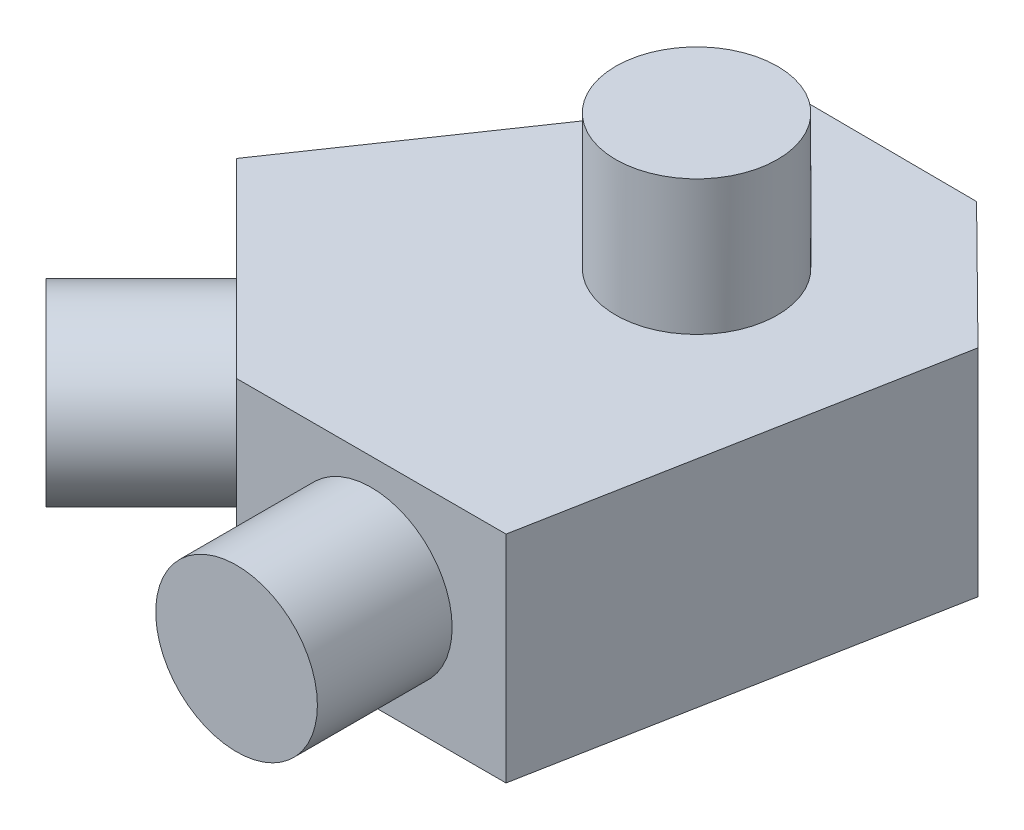
SolidWorks part; units mm, degrees
ref_plane "Front Plane" through (0, 0, 0) normal (0, 0, 1) x (1, 0, 0)
ref_plane "Top Plane" through (0, 0, 0) normal (0, 1, 0) x (1, 0, 0)
ref_plane "Right Plane" through (0, 0, 0) normal (1, 0, 0) x (0, 0, -1)
sketch "Sketch1" plane through (0, 0, 0) normal (0, 1, 0) x (1, 0, 0)
  line L0 (-8.9803, 8.9803) -> (0, 0)
  line L1 (0, 0) -> (12.7, 0)
  line L2 (-8.9803, 8.9803) -> (1.7691, 24.7077)
  line L3 (1.7691, 24.7077) -> (10.2143, 24.6596)
  line L4 (10.2143, 24.6596) -> (16.2201, 18.722)
  line L5 (16.2201, 18.722) -> (12.7, 0)
  line L6 (0, 0) -> (15.9814, 38.5826) construction
  dimension "D1" = 135
  dimension "D2" = 12.7
  dimension "D3" = 12.7
  dimension "D4" = 67.5
  dimension "D5" = 8.4454
  dimension "D6" = 8.4454
  dimension "D7" = 19.05
  dimension "D8" = 19.05
extrude "Boss-Extrude1" add sketch "Sketch1" along normal blind 10.16
sketch "Sketch2" plane through (0, 0, 0) normal (0, 0, 1) x (1, 0, 0)
  line L0 (0, 5.08) -> (15.0157, 5.08) construction
  line L1 (0, 10.16) -> (0, 0) construction
  line L2 (6.35, 10.16) -> (6.35, -2.2419) construction
  line L3 (0, 10.16) -> (12.7, 10.16) construction
  circle A0 centre (6.35, 5.08) radius 3.81
  point P8 (6.35, 5.08)
extrude "Boss-Extrude2" add sketch "Sketch2" along normal blind 6.35 contours A0
sketch "Sketch3" plane through (0, 10.16, 0) normal (0, 1, 0) x (1, 0, 0)
  line L0 (0, 0) -> (10.2143, 24.6596) construction
ref_plane "Plane1" through (0, 0, 0) normal (0.9239, 0, 0.3827) x (0.3827, 0, -0.9239)
mirror "Mirror1" about plane through (0, 0, 0) normal (0.9239, 0, 0.3827) of "Boss-Extrude2"
sketch "Sketch5" plane through (0, 10.16, 0) normal (0, 1, 0) x (1, 0, 0)
  line L0 (6.35, 0) -> (6.35, 28.1321) construction
  line L1 (2.54, 0) -> (10.16, 0) construction
  line L2 (-4.4901, 4.4901) -> (16.6739, 25.6542) construction
  line L3 (-8.9803, 8.9803) -> (0, 0) construction
  circle A0 centre (6.35, 15.3303) radius 3.81
  point P8 (6.35, 15.3303)
  dimension "D1" = 7.62
  dimension "D2" = 16.5933
extrude "Boss-Extrude3" add sketch "Sketch5" along normal blind 6.35
equation "\"H\"=0.332495"
equation "\"D5@Sketch1\"=\"H\""
equation "\"w\"=0.75"
equation "\"D7@Sketch1\"=\"w\""
equation "\"D6@Sketch1\"=\"H\""
equation "\"D8@Sketch1\"=\"w\""
